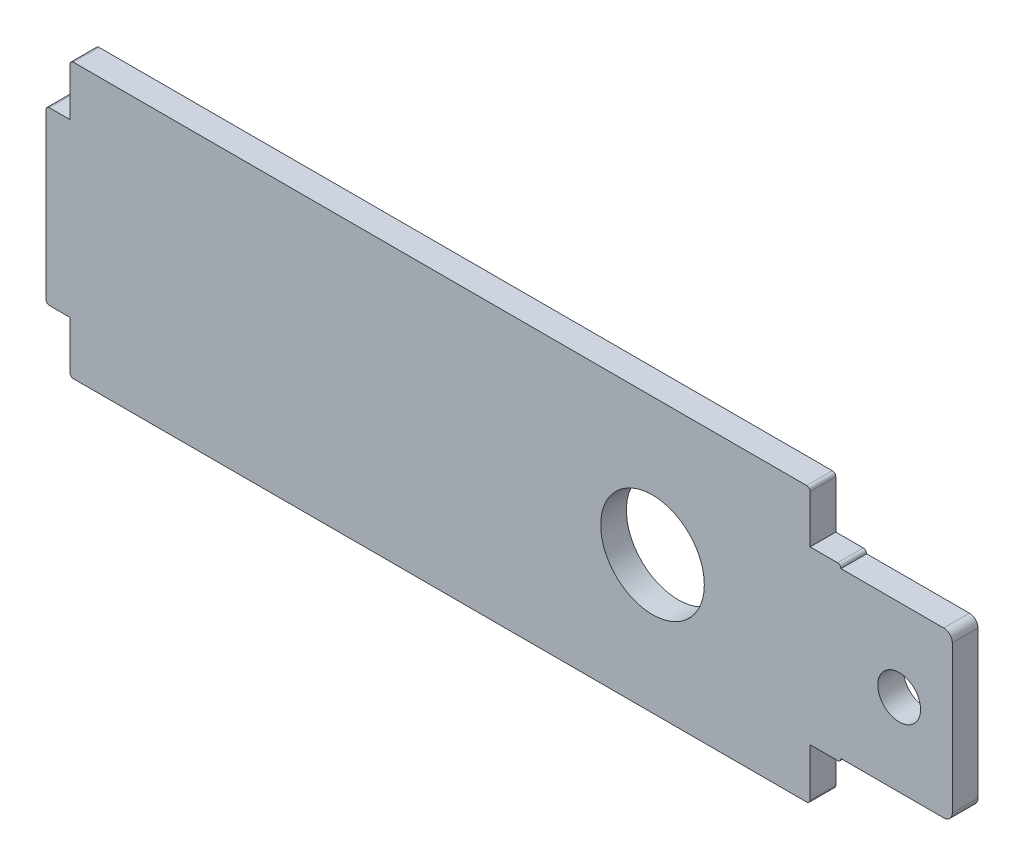
SolidWorks part; units mm, degrees
ref_plane "Front Plane" through (0, 0, 0) normal (0, 0, 1) x (1, 0, 0)
ref_plane "Top Plane" through (0, 0, 0) normal (0, 1, 0) x (1, 0, 0)
ref_plane "Right Plane" through (0, 0, 0) normal (1, 0, 0) x (0, 0, -1)
sketch "Sketch1" plane through (0, 0, 0) normal (0, 0, 1) x (1, 0, 0)
  line L0 (1.4, 17.8) -> (1.4, 15)
  line L1 (1.6, 2) -> (44.4, 2)
  line L2 (0, 5.2) -> (0, 14.8)
  line L3 (1.6, 18) -> (44.4, 18)
  line L4 (46.4, 5.2) -> (46.4, 14.8)
  line L5 (1.4, 15) -> (0.2, 15)
  line L6 (44.6, 17.8) -> (44.6, 15)
  line L7 (44.6, 15) -> (46.2, 15)
  line L8 (0, 10) -> (4.21, 10) construction
  line L9 (1.4, 5) -> (0.2, 5)
  line L10 (1.4, 2.2) -> (1.4, 5)
  line L11 (44.6, 2.2) -> (44.6, 5)
  line L12 (44.6, 5) -> (46.2, 5)
  arc A0 (44.6, 2.2) -> (44.4, 2) centre (44.4, 2.2) cw
  arc A1 (1.4, 2.2) -> (1.6, 2) centre (1.6, 2.2) ccw
  arc A2 (1.4, 17.8) -> (1.6, 18) centre (1.6, 17.8) cw
  arc A3 (44.6, 17.8) -> (44.4, 18) centre (44.4, 17.8) ccw
  arc A4 (46.2, 15) -> (46.4, 14.8) centre (46.2, 14.8) cw
  arc A5 (46.2, 5) -> (46.4, 5.2) centre (46.2, 5.2) ccw
  arc A6 (0.2, 5) -> (0, 5.2) centre (0.2, 5.2) cw
  arc A7 (0.2, 15) -> (0, 14.8) centre (0.2, 14.8) ccw
  circle A8 centre (35.4, 10) radius 3.025
  point P2 (44.6, 2)
  point P20 (1.4, 2)
  point P23 (1.4, 18)
  point P26 (44.6, 18)
  point P29 (46.4, 15)
  point P32 (46.4, 5)
  point P35 (0, 5)
  point P38 (0, 15)
  point P41 (46.4, 10)
  dimension "D7" = 0.2
  dimension "D8" = 6.05
  dimension "D1" = 46.4
  dimension "D2" = 16
  dimension "D3" = 1.4
  dimension "D4" = 1.8
  dimension "D5" = 10
  dimension "D6" = 10
  dimension "D9" = 11
base flange "Base-Flange1" sketch "Sketch1" thickness 1.5 reverse thickness direction no parameters "D1"=2
sketch "Sketch6" plane through (0, 0, 0) normal (0, 0, 1) x (1, 0, 0)
  line L0 (46.4, 14.8) -> (52.4, 14.8)
  line L1 (52.9, 14.3) -> (52.9, 5.7)
  line L2 (52.4, 5.2) -> (46.4, 5.2)
  line L3 (46.4, 14.8) -> (46.4, 5.2)
  arc A0 (52.9, 5.7) -> (52.4, 5.2) centre (52.4, 5.7) cw
  arc A1 (52.4, 14.8) -> (52.9, 14.3) centre (52.4, 14.3) cw
  circle A2 centre (49.8, 10) radius 1.25
  point P8 (52.9, 5.2)
  point P13 (46.4, 10)
  point P14 (52.9, 10)
  dimension "D2" = 0.5
  dimension "D3" = 2.5
  dimension "D4" = 3.4
  dimension "D1" = 6.5
base flange "Tab1" sketch "Sketch6" thickness 1.5 reverse thickness direction no parameters "D1"=2
sketch "Bend-Lines1" [suppressed] plane through (0, 0, 0) normal (0, 1, 0) x (1, 0, 0)
sketch "Bounding-Box1" [suppressed] plane through (0, 0, 0) normal (0, 1, 0) x (1, 0, 0)
sheet metal parameters "Sheet-Metal1" thickness 1.5 parameters "D1"=2
flat pattern "Flat-Pattern1" [suppressed]
sketch "Bend-Lines2" plane through (0, 0, 0) normal (0, 1, 0) x (1, 0, 0)
sketch3d "Bounding-Box2" [suppressed]
  line L0 (-23.9, -0.2, 0) -> (2, -0.2, 0) construction
  line L1 (-23.9, 19.8, 0) -> (2, 19.8, 0) construction
  line L2 (-23.9, -0.2, 0) -> (-23.9, 19.8, 0) construction
  line L3 (2, -0.2, 0) -> (2, 19.8, 0) construction
sheet metal parameters "Sheet-Metal2" thickness 1.5 parameters "D1"=2
flat pattern "Flat-Pattern2"
sketch "Bend-Lines3" plane through (0, 0, 0) normal (0, 1, 0) x (1, 0, 0)
sketch3d "Bounding-Box3" [suppressed]
  line L0 (-20.9, -0.2, 0) -> (8.5, -0.2, 0) construction
  line L1 (-20.9, 15.8, 0) -> (8.5, 15.8, 0) construction
  line L2 (-20.9, -0.2, 0) -> (-20.9, 15.8, 0) construction
  line L3 (8.5, -0.2, 0) -> (8.5, 15.8, 0) construction
